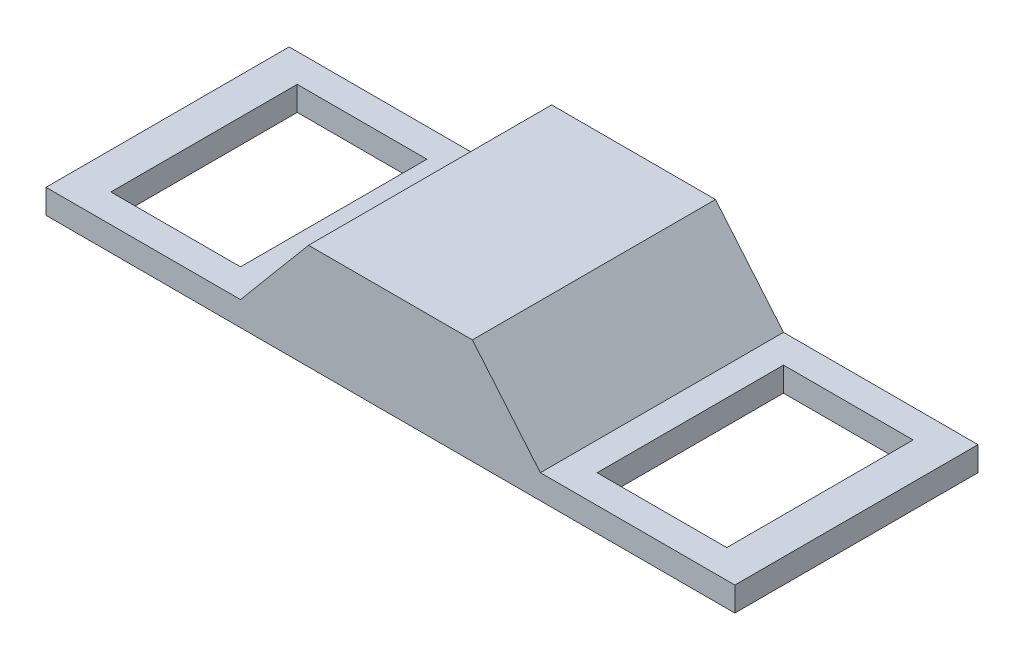
SolidWorks part; units mm, degrees
ref_plane "Front Plane" through (0, 0, 0) normal (0, 0, 1) x (1, 0, 0)
ref_plane "Top Plane" through (0, 0, 0) normal (0, 1, 0) x (1, 0, 0)
ref_plane "Right Plane" through (0, 0, 0) normal (1, 0, 0) x (0, 0, -1)
sketch "Croquis1" plane through (0, 0, 0) normal (0, 1, 0) x (1, 0, 0)
  line L1 (-42.5, -15) -> (42.5, -15)
  line L2 (-42.5, -15) -> (-42.5, 15)
  line L3 (-42.5, 15) -> (42.5, 15)
  line L4 (42.5, -15) -> (42.5, 15)
  line L5 (-42.5, -15) -> (42.5, 15) construction
  line L6 (-42.5, 15) -> (42.5, -15) construction
  line L11 (22, -11.5) -> (22, 11.5)
  line L12 (-38, -11.5) -> (-22, -11.5)
  line L13 (0, 0) -> (0, 50000) construction
  line L18 (-38, -11.5) -> (-38, 11.5)
  line L19 (-38, 11.5) -> (-22, 11.5)
  line L20 (-22, -11.5) -> (-22, 11.5)
  line L21 (-38, -11.5) -> (-22, 11.5) construction
  line L22 (-38, 11.5) -> (-22, -11.5) construction
  line L23 (38, -11.5) -> (22, -11.5)
  line L24 (38, -11.5) -> (38, 11.5)
  line L25 (38, 11.5) -> (22, 11.5)
  point P0 (0, 0)
  point P5 (-30, 0)
  dimension "D1" = 85
  dimension "D2" = 16
  dimension "D3" = 23
  dimension "D4" = 30
extrude "Saliente-Extruir1" add sketch "Croquis1" along normal blind 3
sketch "Croquis3" plane through (0, 3, 0) normal (0, 1, 0) x (1, 0, 0)
  line L0 (42.5, 15) -> (-42.5, 15) construction
  line L1 (-18.5, -15) -> (18.5, -15)
  line L2 (-18.5, -15) -> (-18.5, 15)
  line L3 (-18.5, 15) -> (18.5, 15)
  line L4 (18.5, -15) -> (18.5, 15)
  line L5 (-18.5, -15) -> (18.5, 15) construction
  line L6 (-18.5, 15) -> (18.5, -15) construction
  point P0 (0, 0)
  dimension "D1" = 37
extrude "Saliente-Extruir2" add sketch "Croquis3" along normal blind 10
chamfer "Chaflán1" distance 10 angle 40 2 edges at (18.5, 13, 0) (-18.5, 13, 0) first distance on face at (18.5, 8, 0) first distance on face at (-18.5, 8, 0)
